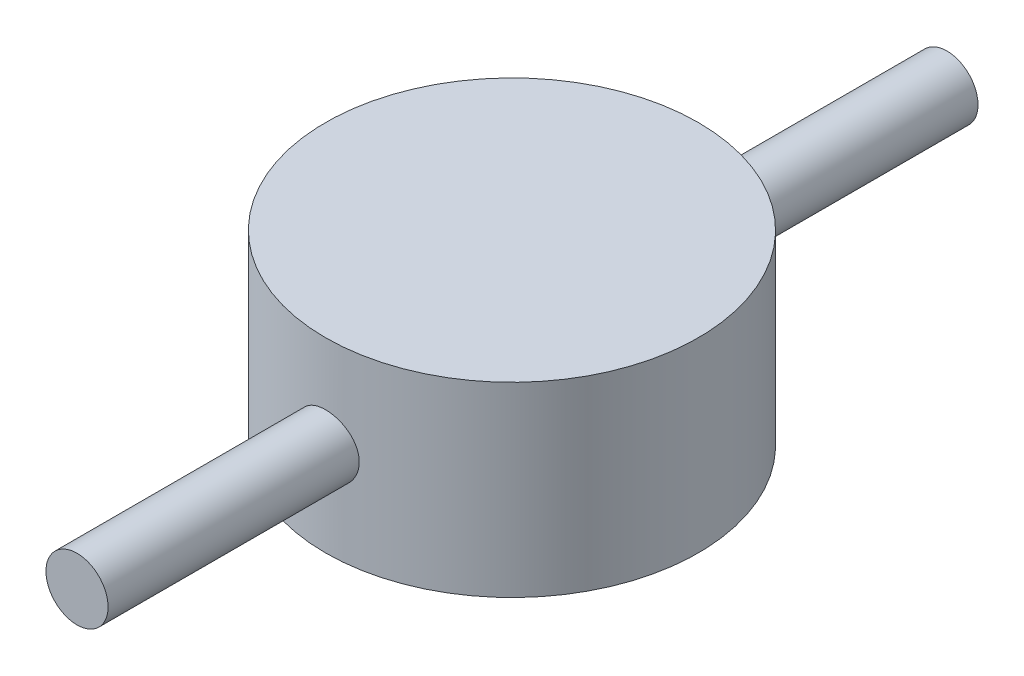
SolidWorks part; units mm, degrees
ref_plane "Front Plane" through (0, 0, 0) normal (0, 0, 1) x (1, 0, 0)
ref_plane "Top Plane" through (0, 0, 0) normal (0, 1, 0) x (1, 0, 0)
ref_plane "Right Plane" through (0, 0, 0) normal (1, 0, 0) x (0, 0, -1)
sketch "Sketch1" plane through (0, 0, 0) normal (0, 1, 0) x (1, 0, 0)
  circle A0 centre (0, 0) radius 15
  dimension "D1" = 30
extrude "Boss-Extrude1" add sketch "Sketch1" along normal blind 15
sketch "Sketch2" plane through (0, 0, 0) normal (0, 0, 1) x (1, 0, 0)
  circle A0 centre (0, 7.4846) radius 2.5
  dimension "D1" = 5
extrude "Boss-Extrude2" add sketch "Sketch2" along normal blind 35 and the other way blind 35
